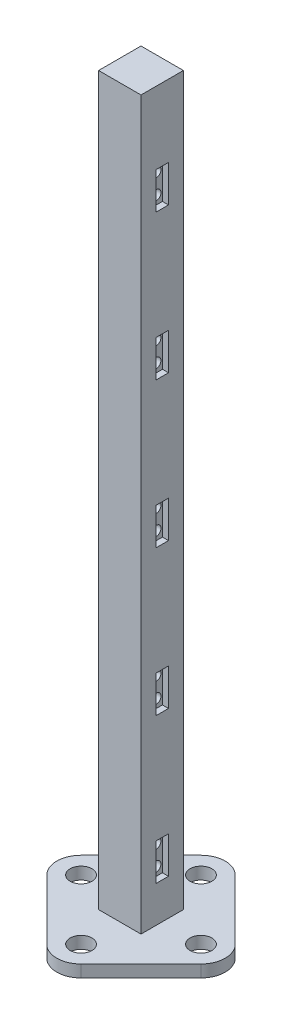
SolidWorks part; units mm, degrees
ref_plane "Front" through (0, 0, 0) normal (0, 0, 1) x (1, 0, 0)
ref_plane "Top" through (0, 0, 0) normal (0, 1, 0) x (1, 0, 0)
ref_plane "Right" through (0, 0, 0) normal (1, 0, 0) x (0, 0, -1)
ref_axis "Axis1" through (0, 55, 0) along (0, -1, 0)
ref_axis "Axis2" through (88.99, 0, 0) along (-1, 0, 0)
ref_axis "Axis3" through (0, 0, 55) along (0, 0, -1)
sketch "Sketch1" plane through (0, 0, 0) normal (0, 1, 0) x (1, 0, 0)
  line L0 (-24.75, 0) -> (0, 24.75) construction
  line L9 (-24.75, 0) -> (0, -24.75) construction
  line L11 (0, 24.75) -> (24.75, 0) construction
  line L12 (0, -24.75) -> (24.75, 0) construction
  line L13 (-24.75, 0) -> (24.75, 0) construction
  line L14 (0, 24.75) -> (0, -24.75) construction
  line L15 (-31.8211, 7.0711) -> (-7.0711, 31.8211)
  line L16 (7.0711, 31.8211) -> (31.8211, 7.0711)
  line L17 (7.0711, -31.8211) -> (31.8211, -7.0711)
  line L18 (-31.8211, -7.0711) -> (-7.0711, -31.8211)
  line L19 (0, -38.8921) -> (38.8921, 0) construction
  line L20 (-38.8921, 0) -> (0, -38.8921) construction
  line L21 (0, 38.8921) -> (38.8921, 0) construction
  line L22 (-38.8921, 0) -> (0, 38.8921) construction
  arc A4 (7.0711, -31.8211) -> (-7.0711, -31.8211) centre (0, -24.75) cw
  arc A5 (31.8211, 7.0711) -> (31.8211, -7.0711) centre (24.75, 0) cw
  arc A6 (-7.0711, 31.8211) -> (7.0711, 31.8211) centre (0, 24.75) cw
  arc A7 (-31.8211, 7.0711) -> (-31.8211, -7.0711) centre (-24.75, 0) ccw
  circle A8 centre (0, 24.75) radius 4.5
  circle A9 centre (24.75, 0) radius 4.5
  circle A10 centre (0, -24.75) radius 4.5
  circle A11 centre (-24.75, 0) radius 4.5
  point P1 (0, 0)
  dimension "D3" = 10
  dimension "D4" = 9
  dimension "D1" = 49.5
  dimension "D2" = 10
extrude "Boss-Extrude1" add sketch "Sketch1" along normal mid plane 5
sketch "Sketch2" plane through (0, 2.5, 0) normal (0, 1, 0) x (1, 0, 0)
  line L0 (-8.75, 8.75) -> (8.75, -8.75) construction
  line L1 (-8.75, 8.75) -> (8.75, 8.75)
  line L2 (-8.75, 8.75) -> (-8.75, -8.75)
  line L3 (-8.75, -8.75) -> (8.75, -8.75)
  line L4 (8.75, 8.75) -> (8.75, -8.75)
  line L5 (-7.0711, 31.8211) -> (-31.8211, 7.0711) construction
  dimension "D1" = 17.5
extrude "Boss-Extrude2" add sketch "Sketch2" along normal blind 300
sketch "Sketch3" plane through (8.75, 0, 0) normal (1, 0, 0) x (0, 0, -1)
  line L0 (7.0711, 2.5) -> (31.8211, 2.5) construction
  line L1 (-2.6, 17.5) -> (2.6, 17.5)
  line L2 (-2.6, 17.5) -> (-2.6, 32.7)
  line L3 (-2.6, 32.7) -> (2.6, 32.7)
  line L4 (2.6, 17.5) -> (2.6, 32.7)
  point P4 (0, 17.5)
  dimension "D1" = 5.2
  dimension "D2" = 15.2
  dimension "D3" = 15
extrude "Cut-Extrude1" cut sketch "Sketch3" against normal blind 2.5
hole_wizard "Ø4.0mm Dowel Hole1" positions "Sketch5" profile "Sketch6" hole size "Ø4.0" standard "DIN" end condition through all
sketch "Sketch5" plane through (6.25, 0, 0) normal (1, 0, 0) x (0, 0, -1)
  line L0 (0, 32.7) -> (0, 29.2) construction
  line L1 (2.6, 32.7) -> (-2.6, 32.7) construction
  line L2 (0, 29.2) -> (0, 21) construction
  line L3 (0, 21) -> (0, 17.5) construction
  line L4 (-2.6, 17.5) -> (2.6, 17.5) construction
  point P0 (0, 21)
  point P2 (0, 29.2)
  dimension "D1" = 3.5
sketch "Sketch6" plane through (6.25, 21, 0) normal (0, 1, 0) x (0, 0, -1)
  line L0 (0, 0) -> (0, 41)
  line L1 (0, 41) -> (2, 41)
  line L2 (2, 41) -> (2, 0)
  line L5 (2, 0) -> (0, 0)
  line L11 (0, -6.35) -> (0, 107.95) construction
  dimension "Thru Hole Dia." = 4
  dimension "Thru Hole Depth" = 41
pattern_linear "LPattern1" count 5 spacing 60 along (0, 1, 0) of "Ø4.0mm Dowel Hole1", "Cut-Extrude1"
